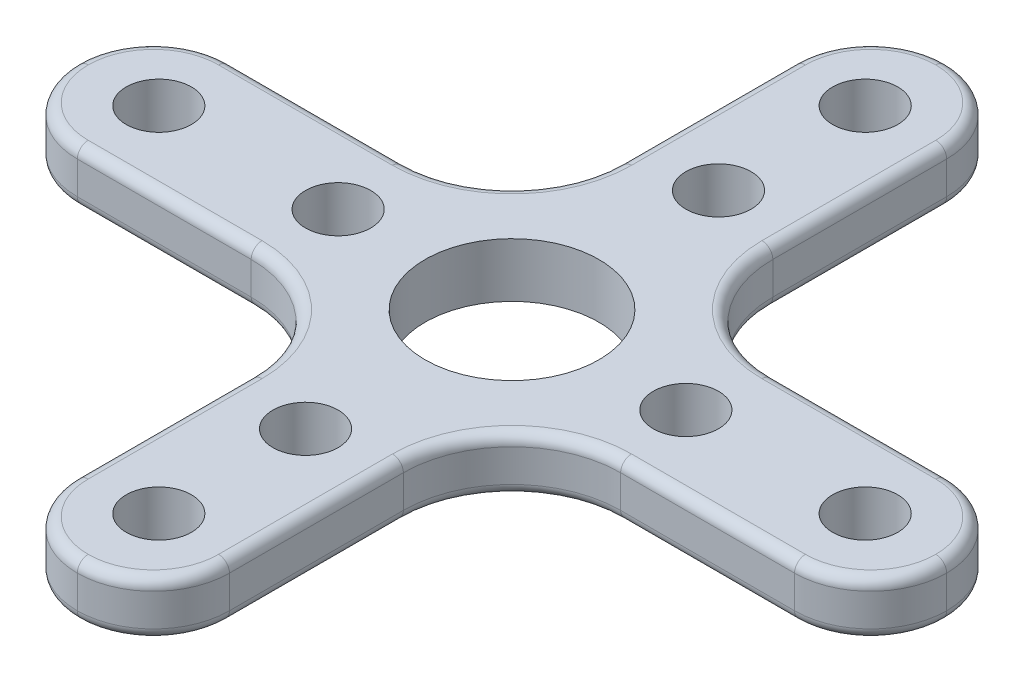
SolidWorks part; units mm, degrees
ref_plane "Front Plane" through (0, 0, 0) normal (0, 0, 1) x (1, 0, 0)
ref_plane "Top Plane" through (0, 0, 0) normal (0, 1, 0) x (1, 0, 0)
ref_plane "Right Plane" through (0, 0, 0) normal (1, 0, 0) x (0, 0, -1)
sketch "Sketch1" plane through (0, 0, 0) normal (0, 1, 0) x (1, 0, 0)
  line L0 (0, -20) -> (0, 20)
  line L1 (-3.5, 20) -> (3.5, 20)
  line L2 (-3.5, 20) -> (-3.5, -20)
  line L3 (-3.5, -20) -> (3.5, -20)
  line L4 (3.5, 20) -> (3.5, -20)
  line L5 (-3.5, 20) -> (3.5, -20) construction
  line L6 (-3.5, -20) -> (3.5, 20) construction
  line L7 (-20, 3.5) -> (20, 3.5)
  line L8 (-20, 3.5) -> (-20, -3.5)
  line L9 (-20, -3.5) -> (20, -3.5)
  line L10 (20, 3.5) -> (20, -3.5)
  line L11 (-20, 3.5) -> (20, -3.5) construction
  line L12 (-20, -3.5) -> (20, 3.5) construction
  line L13 (-20, 0) -> (20, 0)
  circle A1 centre (0, 16.25) radius 1.5
  circle A2 centre (0, 9.5) radius 1.5
  circle A3 centre (0, -9.5) radius 1.5
  circle A4 centre (0, -16.25) radius 1.5
  circle A5 centre (-16.25, 0) radius 1.5
  circle A6 centre (-8, 0) radius 1.5
  circle A7 centre (8, 0) radius 1.5
  circle A8 centre (16.25, 0) radius 1.5
  point P0 (0, 0)
  point P6 (0, 0)
  dimension "D3" = 3
  dimension "D4" = 3
  dimension "D13" = 3
  dimension "D14" = 3
  dimension "D15" = 3
  dimension "D16" = 3
  dimension "D17" = 3
  dimension "D18" = 3
  dimension "D1" = 40
  dimension "D2" = 7
  dimension "D5" = 9.5
  dimension "D6" = 16.25
  dimension "D7" = 16.25
  dimension "D8" = 16.25
  dimension "D9" = 16.25
  dimension "D10" = 9.5
  dimension "D11" = 8
  dimension "D12" = 8
extrude "Boss-Extrude1" add sketch "Sketch1" along normal blind 2.5 contours A6 L13 L2 L7 L8 A5 | A6 L13 A5 L8 L9 L2 | A2 L0 A1 L1 L2 L7 | A2 L0 L7 L4 L1 A1 | A8 L13 L10 L7 L4 A7 | L2 L13 L0 L7 | L13 L2 L9 L0 | L13 L0 L9 L4 | L0 L13 L4 L7 | A4 L0 A3 L9 L2 L3 | A4 L0 L3 L4 L9 A3 | A8 L13 A7 L4 L9 L10 region at (-1.9053, 0, 11.5931) region at (1.9053, 0, 11.5931) region at (-11.6977, 0, 1.9053) region at (-1.75, 0, 1.75) region at (1.75, 0, 1.75) region at (11.6977, 0, 1.9053) region at (-11.6977, 0, -1.9053) region at (-1.75, 0, -1.75) region at (1.75, 0, -1.75) region at (11.6977, 0, -1.9053) region at (-1.9053, 0, -11.5931) region at (1.9053, 0, -11.5931)
fillet "Fillet1" radius 5 4 edges at (-3.5, 1.25, -3.5) (3.5, 1.25, -3.5) (3.5, 1.25, 3.5) (-3.5, 1.25, 3.5)
fillet "Fillet2" radius 3.5 8 edges at (20, 1.25, 3.5) (20, 1.25, -3.5) (3.5, 1.25, -20) (-3.5, 1.25, -20) (-20, 1.25, -3.5) (-20, 1.25, 3.5) (3.5, 1.25, 20) (-3.5, 1.25, 20)
sketch "Sketch2" plane through (0, 2.5, 0) normal (0, 1, 0) x (1, 0, 0)
  circle A0 centre (0, 0) radius 4
  dimension "D1" = 8
extrude "Cut-Extrude1" cut sketch "Sketch2" against normal up to next
fillet "Fillet3" radius 0.5 40 edges at (-12.5, 0, -3.5) (-18.9749, 0, -2.4749) (-18.9749, 0, 2.4749) (-12.5, 0, 3.5) (-4.9645, 0, 4.9645) (-3.5, 0, 12.5) (-2.4749, 0, 18.9749) (2.4749, 0, 18.9749) (3.5, 0, 12.5) (4.9645, 0, 4.9645) (12.5, 0, 3.5) (18.9749, 0, 2.4749) (18.9749, 0, -2.4749) (12.5, 0, -3.5) (4.9645, 0, -4.9645) (3.5, 0, -12.5) (2.4749, 0, -18.9749) (-2.4749, 0, -18.9749) (-3.5, 0, -12.5) (-2.4749, 2.5, -18.9749) (2.4749, 2.5, -18.9749) (3.5, 2.5, -12.5) (4.9645, 2.5, -4.9645) (12.5, 2.5, -3.5) (18.9749, 2.5, -2.4749) (18.9749, 2.5, 2.4749) (12.5, 2.5, 3.5) (4.9645, 2.5, 4.9645) (3.5, 2.5, 12.5) (2.4749, 2.5, 18.9749) (-2.4749, 2.5, 18.9749) (-3.5, 2.5, 12.5) (-4.9645, 2.5, 4.9645) (-12.5, 2.5, 3.5) (-18.9749, 2.5, 2.4749) (-18.9749, 2.5, -2.4749) (-12.5, 2.5, -3.5) (-4.9645, 2.5, -4.9645) (-4.9645, 0, -4.9645) (-3.5, 2.5, -12.5)
